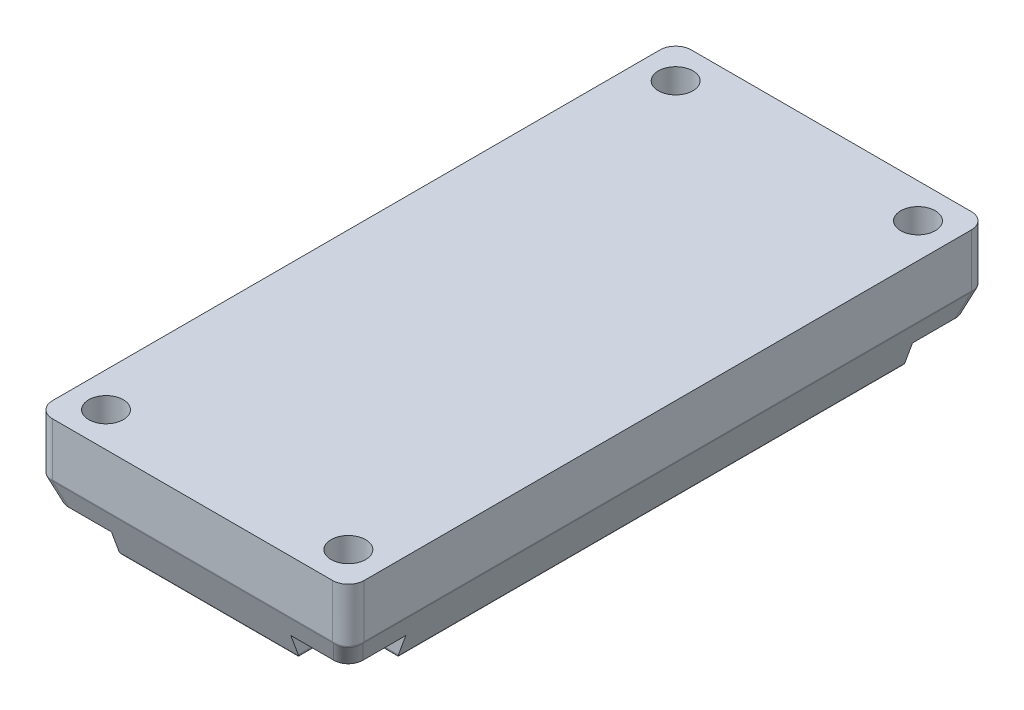
SolidWorks part; units mm, degrees
material "Polyethylene Cross-Linked"
ref_plane "Front Plane" through (0, 0, 0) normal (0, 0, 1) x (1, 0, 0)
ref_plane "Top Plane" through (0, 0, 0) normal (0, 1, 0) x (1, 0, 0)
ref_plane "Right Plane" through (0, 0, 0) normal (1, 0, 0) x (0, 0, -1)
sketch "Sketch1" plane through (0, 0, 0) normal (0, 1, 0) x (1, 0, 0)
  line L1 (-9.9, 20.3) -> (9.9, 20.3)
  line L2 (-9.9, 20.3) -> (-9.9, -20.3)
  line L3 (-9.9, -20.3) -> (9.9, -20.3)
  line L4 (9.9, 20.3) -> (9.9, -20.3)
  line L5 (-9.9, 20.3) -> (9.9, -20.3) construction
  line L6 (-9.9, -20.3) -> (9.9, 20.3) construction
  point P0 (0, 0)
  dimension "D1" = 19.8
  dimension "D2" = 40.6
extrude "Boss-Extrude1" add sketch "Sketch1" against normal blind 6.4
sketch "Sketch2" plane through (0, -6.4, 0) normal (0, -1, 0) x (-1, 0, 0)
  line L0 (5.7, -17.9) -> (5.7, -20.3)
  line L1 (9.9, -20.3) -> (-9.9, -20.3) construction
  line L2 (7.5, -16.1) -> (9.9, -16.1)
  line L3 (9.9, 20.3) -> (9.9, -20.3) construction
  line L4 (5.7, -20.3) -> (9.9, -20.3)
  line L5 (9.9, -20.3) -> (9.9, -16.1)
  arc A0 (7.5, -16.1) -> (5.7, -17.9) centre (7.5, -17.9) ccw
  dimension "D3" = 3.6
  dimension "D1" = 4.2
  dimension "D2" = 4.2
extrude "Cut-Extrude1" cut sketch "Sketch2" against normal blind 1.5
hole_wizard "M2 Clearance Hole1" positions "Sketch8" profile "Sketch7" hole size "M2" standard "ANSI Metric" end condition through all
sketch "Sketch8" plane through (0, -4.9, 0) normal (0, -1, 0) x (-1, 0, 0)
  line L0 (9.9, -20.3) -> (9.9, -16.1) construction
  line L1 (5.7, -20.3) -> (9.9, -20.3) construction
  point P0 (7.7, -18.1)
  dimension "D1" = 2.2
  dimension "D2" = 2.2
sketch "Sketch7" plane through (-7.7, -4.9, 18.1) normal (1, 0, 0) x (0, 0, -1)
  line L0 (0, 0) -> (0, 4.9)
  line L1 (0, 4.9) -> (1.1, 4.9)
  line L2 (1.1, 4.9) -> (1.1, 0)
  line L5 (1.1, 0) -> (0, 0)
  line L11 (0, -6.35) -> (0, 107.95) construction
  dimension "Thru Hole Dia." = 2.2
  dimension "Thru Hole Depth" = 4.9
mirror "Mirror1" about plane through (0, 0, 0) normal (1, 0, 0) of "M2 Clearance Hole1", "Cut-Extrude1"
mirror "Mirror2" about plane through (0, 0, 0) normal (0, 0, 1) of "Mirror1", "Cut-Extrude1"
sketch "Sketch3" plane through (0, 0, 0) normal (0, 0, 1) x (1, 0, 0)
  line L0 (9.9, -3.4) -> (9.9, -6.4)
  line L1 (9.9, -4.9) -> (9.9, 0) construction
  line L2 (9.9, -6.4) -> (8.8081, -6.4)
  line L3 (9.9, -6.4) -> (7.5, -6.4) construction
  line L4 (8.8081, -6.4) -> (9.9, -3.4)
  dimension "D1" = 3
  dimension "D2" = 20
extrude "Cut-Extrude2" cut sketch "Sketch3" against normal through all both and the other way through all
mirror "Mirror3" about plane through (0, 0, 0) normal (1, 0, 0) of "Cut-Extrude2"
sketch "Sketch4" plane through (0, 0, 0) normal (1, 0, 0) x (0, 0, -1)
  line L0 (20.3, -3.4) -> (19.2081, -6.4)
  line L1 (20.3, -3.4) -> (20.3, 0) construction
  line L2 (17.9, -6.4) -> (20.3, -6.4) construction
  line L3 (19.2081, -6.4) -> (20.3, -6.4)
  line L4 (20.3, -6.4) -> (20.3, -3.4)
  dimension "D1" = 3
  dimension "D2" = 20
extrude "Cut-Extrude3" cut sketch "Sketch4" against normal through all both and the other way through all
mirror "Mirror4" about plane through (0, 0, 0) normal (0, 0, 1) of "Cut-Extrude3"
fillet "Fillet1" radius 1 8 edges at (-9.627, -4.15, -20.027) (-9.9, -1.7, -20.3) (9.9, -1.7, -20.3) (9.627, -4.15, -20.027) (9.627, -4.15, 20.027) (9.9, -1.7, 20.3) (-9.9, -1.7, 20.3) (-9.627, -4.15, 20.027)
fillet "Fillet2" radius 0.2 32 edges at (-8.9293, -3.4012, 20.2996) (-9.6071, -3.4659, 20.0071) (-9.8996, -3.4012, 19.3293) (-9.9, -3.4, 0) (-9.8996, -3.4012, -19.3293) (-9.6071, -3.4659, -20.0071) (-8.9293, -3.4012, -20.2996) (0, -3.4, -20.3) (8.9293, -3.4012, -20.2996) (9.6071, -3.4659, -20.0071) (9.8996, -3.4012, -19.3293) (9.9, -3.4, 0) (9.8996, -3.4012, 19.3293) (9.6071, -3.4659, 20.0071) (8.9293, -3.4012, 20.2996) (5.7, -6.4, 18.554) (6.2272, -6.4, 16.6272) (8.154, -6.4, 16.1) (8.8081, -6.4, 0) (8.154, -6.4, -16.1) (6.2272, -6.4, -16.6272) (5.7, -6.4, -18.554) (0, -6.4, -19.2081) (-5.7, -6.4, -18.554) (-6.2272, -6.4, -16.6272) (-8.154, -6.4, -16.1) (-8.8081, -6.4, 0) (-8.154, -6.4, 16.1) (-6.2272, -6.4, 16.6272) (-5.7, -6.4, 18.554) (0, -6.4, 19.2081) (0, -3.4, 20.3)
move or copy body "Body-Move/Copy1" [suppressed] bodies to move or copy 139
move or copy body "Body-Move/Copy2" [suppressed] bodies to move or copy 141
